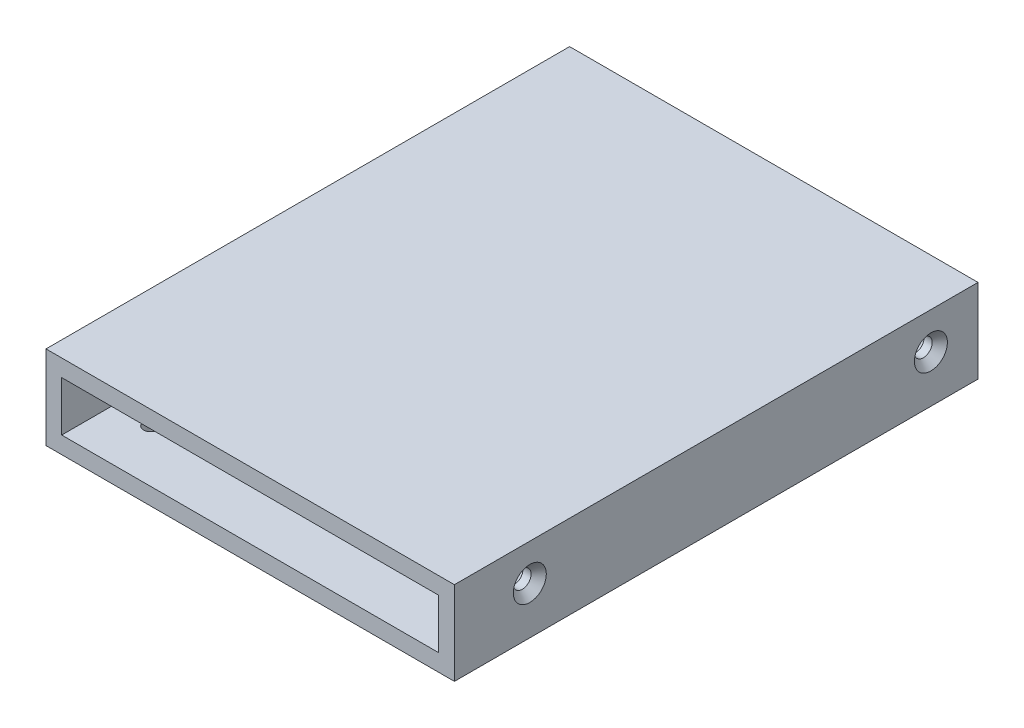
SolidWorks part; units mm, degrees
ref_plane "Plan de face" through (0, 0, 0) normal (0, 0, 1) x (1, 0, 0)
ref_plane "Plan de dessus" through (0, 0, 0) normal (0, 1, 0) x (1, 0, 0)
ref_plane "Plan de droite" through (0, 0, 0) normal (1, 0, 0) x (0, 0, -1)
sketch "Main-Sketch" plane through (0, 0, 0) normal (0, 0, 1) x (1, 0, 0)
  line L1 (0, 0) -> (78, 0)
  line L2 (0, 0) -> (0, 16)
  line L3 (0, 16) -> (78, 16)
  line L4 (78, 0) -> (78, 16)
  line L5 (3, 12.75) -> (75, 12.75)
  line L6 (3, 12.75) -> (3, 3.25)
  line L7 (3, 3.25) -> (75, 3.25)
  line L8 (75, 12.75) -> (75, 3.25)
  point P9 (39, 12.75)
  point P10 (39, 16)
  point P11 (3, 8)
  point P12 (0, 8)
  dimension "D1" = 78
  dimension "D2" = 16
  dimension "D3" = 72
  dimension "D4" = 9.5
extrude "Main-Extrusion" add sketch "Main-Sketch" along normal blind 100
hole_wizard "Fraisage pour vis à tête fraisée M31" positions "Esquisse3" profile "Esquisse4" countersink size "M3" standard "Ansi Metric" end condition through all
sketch "Esquisse3" plane through (0, 0, 0) normal (-1, 0, 0) x (0, 0, 1)
  line L0 (100, 0) -> (0, 0) construction
  line L1 (0, 16) -> (0, 0) construction
  point P0 (9, 9)
  point P9 (9.5176, 9)
  point P14 (9.3093, 8.1276)
  dimension "D1" = 9
  dimension "D2" = 9
sketch "Esquisse4" plane through (0, 9, 9) normal (0, 1, 0) x (0, 0, 1)
  line L0 (0, 0) -> (0, 78)
  line L1 (0, 78) -> (1.7, 78)
  line L2 (1.7, 78) -> (1.7, 1.45)
  line L3 (1.7, 1.45) -> (3.15, 0)
  line L5 (3.15, 0) -> (0, 0)
  line L6 (-1.7, 1.45) -> (-3.15, 0) construction
  line L11 (0, -6.35) -> (0, 107.95) construction
  dimension "Diamètre du perçage jusqu'au prochain" = 3.4
  dimension "Profondeur du perçage jusqu'au prochain" = 78
  dimension "Diamètre du fraisage entrant" = 6.3
  dimension "Angle du fraisage entrant" = 90
pattern_linear "Répétition linéaire1" count 2 spacing 76.6 along (0, 0, 1) of "Fraisage pour vis à tête fraisée M31"
hole_wizard "Fraisage pour vis à tête fraisée M32" positions "Esquisse7" profile "Esquisse8" countersink size "M3" standard "Ansi Metric" end condition through all
sketch "Esquisse7" plane through (78, 0, 0) normal (1, 0, 0) x (0, 0, -1)
  point P0 (-85.6, 9)
  point P3 (-85.5, 9)
sketch "Esquisse8" plane through (78, 9, 85.6) normal (0, 1, 0) x (0, 0, -1)
  line L0 (0, 0) -> (0, 154.5)
  line L1 (0, 154.5) -> (1.7, 154.5)
  line L2 (1.7, 154.5) -> (1.7, 1.45)
  line L3 (1.7, 1.45) -> (3.15, 0)
  line L5 (3.15, 0) -> (0, 0)
  line L6 (-1.7, 1.45) -> (-3.15, 0) construction
  line L11 (0, -6.35) -> (0, 107.95) construction
  dimension "Diamètre du perçage jusqu'au prochain" = 3.4
  dimension "Profondeur du perçage jusqu'au prochain" = 154.5
  dimension "Diamètre du fraisage entrant" = 6.3
  dimension "Angle du fraisage entrant" = 90
pattern_linear "Répétition linéaire3" count 2 spacing 76.5 along (1, 0, 0) of "Fraisage pour vis à tête fraisée M32"
hole_wizard "Fraisage pour vis à tête fraisée M33" positions "Esquisse9" profile "Esquisse10" countersink size "M3" standard "Ansi Metric" end condition through all
sketch "Esquisse9" plane through (78, 0, 0) normal (1, 0, 0) x (0, 0, -1)
  point P0 (-9, 9)
sketch "Esquisse10" plane through (78, 9, 9) normal (0, 1, 0) x (0, 0, -1)
  line L0 (0, 0) -> (0, 78)
  line L1 (0, 78) -> (1.7, 78)
  line L2 (1.7, 78) -> (1.7, 1.45)
  line L3 (1.7, 1.45) -> (3.15, 0)
  line L5 (3.15, 0) -> (0, 0)
  line L6 (-1.7, 1.45) -> (-3.15, 0) construction
  line L11 (0, -6.35) -> (0, 107.95) construction
  dimension "Diamètre du perçage jusqu'au prochain" = 3.4
  dimension "Profondeur du perçage jusqu'au prochain" = 78
  dimension "Diamètre du fraisage entrant" = 6.3
  dimension "Angle du fraisage entrant" = 90
sketch "Support-Fix-Sketch" plane through (0, 0, 0) normal (0, -1, 0) x (1, 0, 0)
  line L0 (0, 100) -> (0, 0) construction
  line L1 (78, 100) -> (78, 0) construction
  line L2 (0, 0) -> (78, 0) construction
  line L3 (0, 100) -> (78, 100) construction
  circle A0 centre (68, 90) radius 1.35
  circle A1 centre (68, 10) radius 1.35
  circle A2 centre (10, 10) radius 1.35
  circle A3 centre (10, 90) radius 1.35
  point P8 (0, 0)
  point P15 (0, 0)
  point P18 (0, 0)
  point P19 (0, 0)
  dimension "D1" = 2.7
  dimension "D2" = 10
  dimension "D3" = 10
  dimension "D4" = 10
  dimension "D5" = 10
  dimension "D6" = 58
  dimension "D7" = 80
extrude "Support-Fix-Hole" cut sketch "Support-Fix-Sketch" against normal up to next
